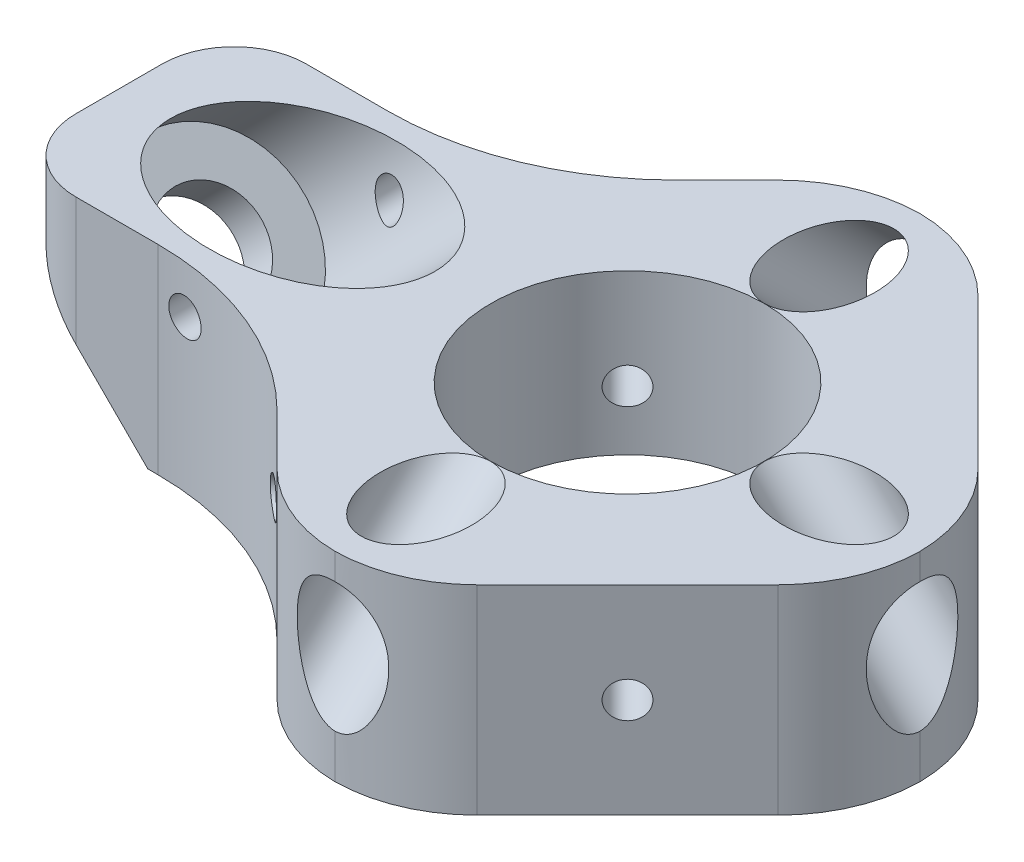
SolidWorks part; units mm, degrees
ref_plane "Front Plane" through (0, 0, 0) normal (0, 0, 1) x (1, 0, 0)
ref_plane "Top Plane" through (0, 0, 0) normal (0, 1, 0) x (1, 0, 0)
ref_plane "Right Plane" through (0, 0, 0) normal (1, 0, 0) x (0, 0, -1)
other "Center of Mass"
sketch "Sketch1" plane through (0, 0, 0) normal (0, 1, 0) x (1, 0, 0)
  line L0 (-35.32, 0) -> (-20.32, 0) construction
  line L1 (20.32, -20.32) -> (-20.32, -20.32)
  line L2 (20.32, -20.32) -> (20.32, 20.32)
  line L3 (20.32, 20.32) -> (-20.32, 20.32)
  line L4 (-20.32, -20.32) -> (-20.32, -8)
  line L5 (20.32, -20.32) -> (-20.32, 20.32) construction
  line L6 (20.32, 20.32) -> (-20.32, -20.32) construction
  line L7 (-20.32, 8) -> (-35.32, 8)
  line L9 (-20.32, -8) -> (-35.32, -8)
  line L10 (-35.32, 8) -> (-35.32, -8)
  line L11 (-20.32, 8) -> (-20.32, 20.32)
  point P0 (0, 0)
  dimension "D1" = 40.64
  dimension "D2" = 40.64
  dimension "D3" = 15
  dimension "D4" = 16
extrude "Boss-Extrude1" add sketch "Sketch1" along normal blind 13.86
sketch "Sketch4" plane through (0, 13.86, 0) normal (0, 1, 0) x (1, 0, 0)
  line L0 (20.32, -20.32) -> (20.32, 20.32) construction
  line L1 (-20.32, -20.32) -> (20.32, -20.32) construction
  line L2 (-20.32, -8) -> (-20.32, -20.32) construction
  circle A0 centre (15, 15) radius 3.25
  circle A1 centre (-15, 15) radius 3.25
  circle A2 centre (15, -15) radius 3.25
  circle A3 centre (-15, -15) radius 3.25
  circle A4 centre (0, 0) radius 14
  dimension "D1" = 6.5
  dimension "D2" = 6.5
  dimension "D3" = 6.5
  dimension "D4" = 6.5
  dimension "D5" = 28
  dimension "D6" = 29.9999
  dimension "D7" = 29.9999
  dimension "D8" = 29.9999
  dimension "D9" = 29.9999
  dimension "D10" = 5.32
  dimension "D11" = 5.32
  dimension "D12" = 5.32
  dimension "D13" = 5.32
sketch "Sketch20" plane through (0, 0, 0) normal (0, -1, 0) x (1, 0, 0)
  circle A0 centre (0, 0) radius 15.5
  dimension "D1" = 31
extrude "Cut-Extrude14" cut sketch "Sketch20" against normal blind 2.79
chamfer "Chamfer1" distance 10 angle 45 4 edges at (20.32, 6.93, 20.32) (-20.32, 6.93, 20.32) (20.32, 6.93, -20.32) (-20.32, 6.93, -20.32)
fillet "Fillet1" radius 2 8 edges at (20.32, 6.93, -10.32) (20.32, 6.93, 10.32) (10.32, 6.93, 20.32) (-10.32, 6.93, 20.32) (-20.32, 6.93, 10.32) (10.32, 6.93, -20.32) (-10.32, 6.93, -20.32) (-20.32, 6.93, -10.32)
sketch "Sketch5" plane through (-15.32, 0, -15.32) normal (-0.7071, 0, -0.7071) x (-0.7071, 0, 0.7071)
  line L0 (0, 0) -> (0, 13.86) construction
  line L1 (14, 13.86) -> (-14, 13.86) construction
  circle A0 centre (0, 6.93) radius 1.25
  dimension "D1" = 2.5
extrude "Cut-Extrude1" cut sketch "Sketch5" against normal through all
ref_axis "Axis1" through (0, 13.86, 0) along (0, 1, 0)
pattern_circular "CirPattern1" count 4 over 360 about axis through (0, 13.86, 0) along (0, 1, 0) of "Cut-Extrude1"
sketch "Sketch6" plane through (0, 0, 0) normal (0, 0, 1) x (1, 0, 0)
  line L0 (27.86, 13.86) -> (27.86, 0)
  line L1 (10.9058, 0) -> (19.7342, 0) construction
  line L2 (27.86, 0) -> (0, 0)
  line L3 (27.86, 0) -> (14, 13.86)
  line L8 (18.25, 13.86) -> (11.75, 13.86) construction
  dimension "D1" = 45
ref_plane "Plane1" through (14, 13.86, 0) normal (-0.7071, 0.7071, 0) x (-0.7071, -0.7071, 0)
sketch "Sketch9" plane through (0, 13.86, 0) normal (0, 1, 0) x (1, 0, 0)
  circle A0 centre (0, 0) radius 9.5
  dimension "D1" = 19
extrude "Cut-Extrude4" cut sketch "Sketch9" against normal through all
sketch "Sketch19" plane through (0, 13.86, 0) normal (0, 1, 0) x (1, 0, 0)
  line L0 (-20.32, -8) -> (-17.4037, -8)
  line L1 (-17.4037, -8) -> (-5.0837, -20.32) construction
  line L2 (-9.4916, -20.32) -> (9.4916, -20.32) construction
  line L3 (-16.3431, -8) -> (-4.0231, -20.32)
  line L4 (-15, -15) -> (-12.1715, -12.1715) construction
  line L5 (-17.4037, -8) -> (-16.3431, -8)
  line L6 (-4.0231, -20.32) -> (-20.32, -20.32)
  line L7 (-20.32, -20.32) -> (-20.32, -8)
  circle A0 centre (-15, -15) radius 3.25 construction
  dimension "D1" = 4
sketch "Sketch10" plane through (0, 13.86, 0) normal (0, 1, 0) x (1, 0, 0)
  line L0 (15, -15) -> (0, 0) construction
  line L1 (0, 0) -> (15, 15) construction
  line L2 (10.9058, -19.7342) -> (19.7342, -10.9058) construction
  line L3 (0, 0) -> (-15, 15)
  line L4 (20.32, -9.4916) -> (20.32, 9.4916) construction
  line L5 (0, 0) -> (-15, -15)
  line L6 (20.32, -4.0231) -> (4.0231, -20.32)
  line L7 (-9.4916, -20.32) -> (9.4916, -20.32) construction
  line L8 (20.32, -4.0231) -> (20.32, -20.32)
  line L9 (20.32, -20.32) -> (4.0231, -20.32)
  circle A3 centre (15, -15) radius 3.25 construction
  point P9 (12.1715, -12.1715)
  point P30 (0, 0)
  line M5 (20.32, -9.4916) -> (20.32, 9.4916)
  line M17 (-9.4916, -20.32) -> (9.4916, -20.32)
  arc M18 (9.4916, -20.32) -> (10.9058, -19.7342) centre (9.4916, -18.32) ccw
  line M19 (10.9058, -19.7342) -> (19.7342, -10.9058)
  arc M20 (19.7342, -10.9058) -> (20.32, -9.4916) centre (18.32, -9.4916) ccw
  dimension "D1" = 4
extrude "Cut-Extrude5" cut sketch "Sketch10" against normal through all contours L6 M5 M17 M18 M19 M20 region at (13.6168, 13.86, 13.6168)
pattern_circular "CirPattern3" count 2 every 90 about axis through (0, 13.86, 0) along (0, 1, 0) of "Cut-Extrude5"
sketch "Sketch14" plane through (0, 0, 0) normal (0, 0, 1) x (1, 0, 0)
  line L0 (-35.32, 0) -> (0, 0) construction
  line L1 (-35.32, 0) -> (-6.7451, 28.5749) construction
  dimension "D1" = 45
sketch "Sketch7" plane through (14, 13.86, 0) normal (-0.7071, 0.7071, 0) x (-0.7071, -0.7071, 0)
  line L0 (0, 0) -> (19.7, 0) construction
  circle A0 centre (0, 0) radius 3.18
  dimension "D1" = 6.36
extrude "Cut-Extrude2" cut sketch "Sketch7" against normal through all both and the other way through all contours A0
pattern_circular "CirPattern2" count 2 every 90 about axis through (0, 13.86, 0) along (0, 1, 0) of "Cut-Extrude2" other way count 2
extrude "Cut-Extrude9" cut sketch "Sketch19" against normal through all
mirror "Mirror1" about plane through (0, 0, 0) normal (0, 0, 1) of "Cut-Extrude9"
fillet "Fillet2" radius 20 2 edges at (-16.3431, 6.93, -8) (-16.3431, 6.93, 8)
fillet "Fillet3" radius 10 6 edges at (-4.0231, 6.93, -20.32) (4.0231, 6.93, -20.32) (20.32, 6.93, -4.0231) (20.32, 6.93, 4.0231) (4.0231, 6.93, 20.32) (-4.0231, 6.93, 20.32)
fillet "Fillet4" radius 5 2 edges at (-35.32, 6.93, -8) (-35.32, 6.93, 8)
sketch "Sketch27" plane through (0, 0, 0) normal (0, 0, 1) x (1, 0, 0)
  circle A0 centre (-22.5962, 10.5556) radius 1.25
  dimension "D1" = 2.5
extrude "Cut-Extrude13" cut sketch "Sketch27" against normal through all both and the other way through all
ref_plane "Plane2" through (-35.32, 13.86, 0) normal (0.7071, 0.7071, 0) x (0.7071, -0.7071, 0)
sketch "Sketch30" plane through (-35.32, 13.86, 0) normal (0.7071, 0.7071, 0) x (0.7071, -0.7071, 0)
  line L0 (24.975, 0) -> (8.8972, 0) construction
  circle A0 centre (9.0236, 0) radius 3.5
  dimension "D1" = 7
extrude "Cut-Extrude15" cut sketch "Sketch30" against normal through all both and the other way through all
ref_axis "Axis2" through (-35.32, 13.86, 0) along (1, 0, 0)
ref_plane "Plane3" through (-24.0063, 25.1737, 0) normal (0.7071, 0.7071, 0) x (0.7071, -0.7071, 0)
sketch "Sketch31" plane through (-24.0063, 25.1737, 0) normal (0.7071, 0.7071, 0) x (0.7071, -0.7071, 0)
  circle A0 centre (9.0236, 0) radius 6.5
  dimension "D1" = 13
extrude "Cut-Extrude16" cut sketch "Sketch31" against normal up to surface (16 mm away) up to plane "Plane2"
sketch "Sketch32" plane through (0, 0, 0) normal (0, 0, 1) x (1, 0, 0)
  line L2 (-35.32, 10) -> (-35.32, 0)
  line L3 (-35.32, 0) -> (-25.32, 0)
  line L7 (-35.32, 10) -> (-25.32, 0)
  line L10 (-35.32, 0) -> (0, 0) construction
  dimension "D1" = 10
  dimension "D2" = 10
extrude "Cut-Extrude17" cut sketch "Sketch32" against normal through all both and the other way through all
